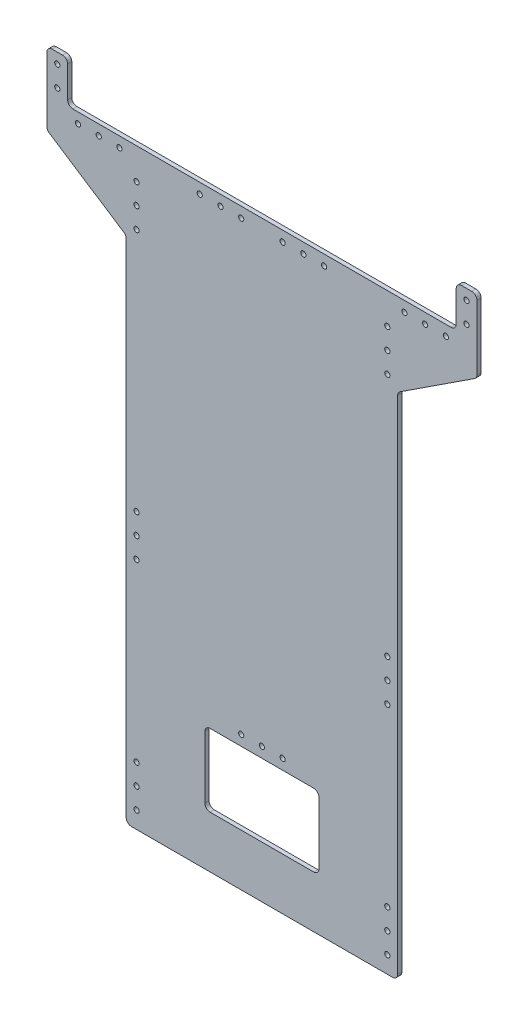
SolidWorks part; units mm, degrees
ref_plane "Front Plane" through (0, 0, 0) normal (0, 0, 1) x (1, 0, 0)
ref_plane "Top Plane" through (0, 0, 0) normal (0, 1, 0) x (1, 0, 0)
ref_plane "Right Plane" through (0, 0, 0) normal (1, 0, 0) x (0, 0, -1)
sketch "Sketch1" plane through (0, 0, 0) normal (0, 0, 1) x (1, 0, 0)
  line L9 (0, -55) -> (0, 55) construction
  line L16 (131, 491.5) -> (131, 0)
  line L18 (-131, 0) -> (-131, 491.5)
  line L22 (207.5, 541.5) -> (207.5, 611.5)
  line L34 (207.5, 611.5) -> (187.5, 611.5)
  line L35 (187.5, 611.5) -> (187.5, 571.5)
  line L37 (187.5, 571.5) -> (-187.5, 571.5)
  line L41 (-187.5, 571.5) -> (-187.5, 611.5)
  line L42 (-187.5, 611.5) -> (-207.5, 611.5)
  line L43 (-207.5, 611.5) -> (-207.5, 541.5)
  line L44 (207.5, 541.5) -> (131, 491.5)
  line L45 (-207.5, 541.5) -> (-131, 491.5)
  line L47 (55, 120) -> (-55, 120)
  line L49 (131, 0) -> (-131, 0)
  line L50 (121, 16.3459) -> (121, 36.3459) construction
  line L51 (121, 225.75) -> (121, 245.75) construction
  line L52 (121, 541.5) -> (121, 521.5) construction
  line L53 (-121, 16.3459) -> (-121, 36.3459) construction
  line L54 (-121, 225.75) -> (-121, 245.75) construction
  line L55 (-121, 541.5) -> (-121, 521.5) construction
  line L56 (177.5, 561.5) -> (157.5, 561.5) construction
  line L58 (55, 120) -> (-55, 120)
  line L59 (55, 120) -> (55, 50)
  line L60 (55, 50) -> (-55, 50)
  line L61 (-55, 120) -> (-55, 50)
  circle A4 centre (197.5, 601.5) radius 2.5
  circle A5 centre (197.5, 581.5) radius 2.5
  circle A6 centre (-197.5, 581.5) radius 2.5
  circle A7 centre (-197.5, 601.5) radius 2.5
  circle A8 centre (60, 561.5) radius 2.5
  circle A9 centre (40, 561.5) radius 2.5
  circle A10 centre (20, 561.5) radius 2.5
  circle A11 centre (-20, 561.5) radius 2.5
  circle A12 centre (-40, 561.5) radius 2.5
  circle A13 centre (-60, 561.5) radius 2.5
  circle A14 centre (121, 16.3459) radius 2.5
  circle A15 centre (121, 36.3459) radius 2.5
  circle A16 centre (121, 56.3459) radius 2.5
  circle A17 centre (121, 225.75) radius 2.5
  circle A18 centre (121, 245.75) radius 2.5
  circle A19 centre (121, 265.75) radius 2.5
  circle A22 centre (121, 541.5) radius 2.5
  circle A23 centre (121, 521.5) radius 2.5
  circle A24 centre (121, 501.5) radius 2.5
  circle A25 centre (-121, 56.3459) radius 2.5
  circle A26 centre (-121, 36.3459) radius 2.5
  circle A27 centre (-121, 16.3459) radius 2.5
  circle A28 centre (-121, 265.75) radius 2.5
  circle A29 centre (-121, 245.75) radius 2.5
  circle A30 centre (-121, 225.75) radius 2.5
  circle A31 centre (-121, 501.5) radius 2.5
  circle A32 centre (-121, 521.5) radius 2.5
  circle A33 centre (-121, 541.5) radius 2.5
  circle A34 centre (177.5, 561.5) radius 2.5
  circle A35 centre (157.5, 561.5) radius 2.5
  circle A36 centre (137.5, 561.5) radius 2.5
  circle A37 centre (-157.5, 561.5) radius 2.5
  circle A38 centre (-177.5, 561.5) radius 2.5
  circle A39 centre (-137.5, 561.5) radius 2.5
  circle A41 centre (-20, 130) radius 2.5
  circle A42 centre (0, 130) radius 2.5
  circle A43 centre (20, 130) radius 2.5
  point P8 (0, 120)
  point P16 (197.5, 611.5)
  point P43 (0, 571.5)
  point P54 (131, 245.75)
  point P110 (-197.5, 611.5)
  point P111 (0, 0)
  point P114 (0, 0)
  dimension "D6" = 5
  dimension "D1" = 76.5
  dimension "D2" = 20
  dimension "D3" = 262
  dimension "D4" = 30
  dimension "D7" = 10
  dimension "D8" = 20
  dimension "D9" = 40
  dimension "10" = 110
  dimension "D15" = 20
  dimension "D16" = 20
  dimension "D17" = 20
  dimension "D18" = 20
  dimension "D19" = 40
  dimension "D20" = 20
  dimension "D21" = 10
  dimension "D23" = 10
  dimension "D24" = 20
  dimension "D25" = 20
  dimension "D26" = 20
  dimension "D29" = 20
  dimension "D30" = 10
  dimension "D31" = 20
  dimension "D33" = 20
  dimension "D34" = 20
  dimension "D35" = 10
  dimension "D5" = 571.5
  dimension "D10" = 50
  dimension "D12" = 16.3459
  dimension "D14" = 70
  dimension "D11" = 30
  dimension "D13" = 50
  dimension "D27" = 3
  dimension "D22" = 3
  dimension "D32" = 3
extrude "Boss-Extrude1" add sketch "Sketch1" against normal blind 4 contours L49 L16 L44 L22 L34 L35 L37 L41 L42 L43 L45 L18 A43 A42 A41 A38 A33 A31 A29 A27 A25 A24 A23 A22 A19 A18 A17 A16 A15 A14 A13 region at (0, 312.9683, 0)
fillet "Fillet1" radius 5 16 edges at (55, 120, -2) (55, 50, -2) (-55, 50, -2) (-55, 120, -2) (-187.5, 571.5, -2) (-187.5, 611.5, -2) (-207.5, 611.5, -2) (-207.5, 541.5, -2) (-131, 491.5, -2) (-131, 0, -2) (131, 0, -2) (131, 491.5, -2) (207.5, 541.5, -2) (187.5, 571.5, -2) (187.5, 611.5, -2) (207.5, 611.5, -2)
equation "\"D16@Sketch1\"=\"D15@Sketch1\""
equation "\"D17@Sketch1\"=\"D15@Sketch1\""
equation "\"D18@Sketch1\"=\"D15@Sketch1\""
